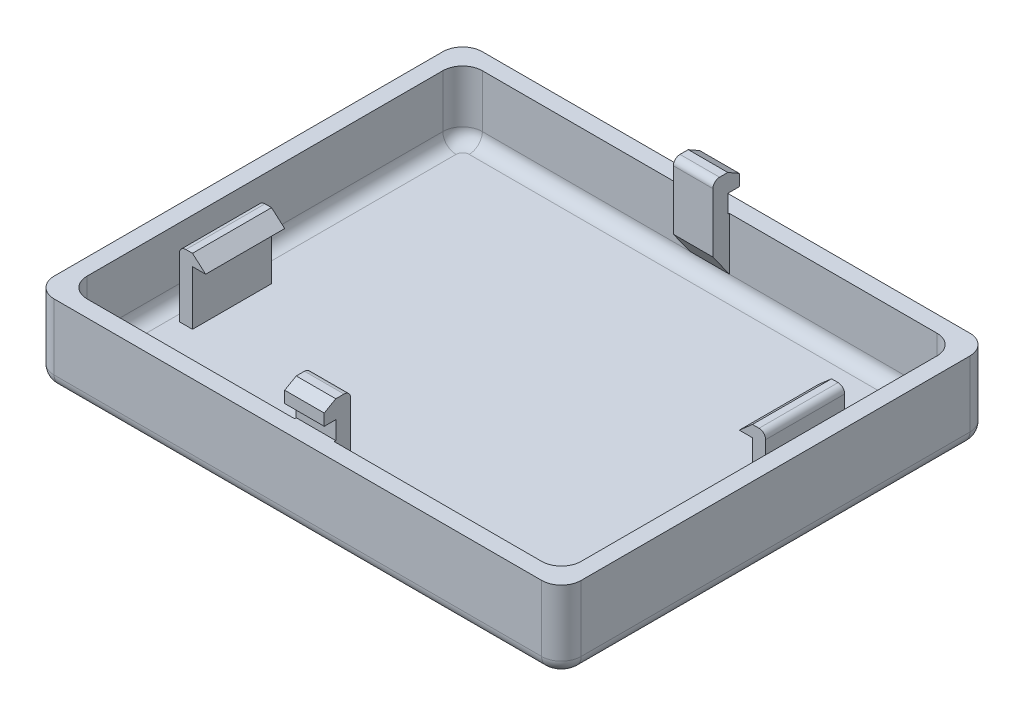
SolidWorks part; units mm, degrees
ref_plane "Front Plane" through (0, 0, 0) normal (0, 0, 1) x (1, 0, 0)
ref_plane "Top Plane" through (0, 0, 0) normal (0, 1, 0) x (1, 0, 0)
ref_plane "Right Plane" through (0, 0, 0) normal (1, 0, 0) x (0, 0, -1)
sketch "Sketch1" plane through (0, 0, 0) normal (0, 1, 0) x (1, 0, 0)
  line L0 (0, 0) -> (80, 0)
  line L1 (80, 0) -> (80, 65)
  line L2 (80, 65) -> (0, 65)
  line L3 (0, 65) -> (0, 0)
  dimension "D1" = 80
  dimension "D2" = 65
extrude "Boss-Extrude1" add sketch "Sketch1" along normal blind 12
sketch "Sketch2" plane through (0, 12, 0) normal (0, 1, 0) x (1, 0, 0)
  line L0 (0, 0) -> (77.5, 0)
  line L1 (0, 0) -> (80, 0) construction
  line L2 (77.5, 0) -> (77.5, 62.5)
  line L3 (77.5, 62.5) -> (2.5, 62.5)
  line L4 (2.5, 62.5) -> (2.5, 0)
  line L5 (2.5, 2.5) -> (77.5, 2.5)
  line L6 (0, 65) -> (0, 0) construction
  dimension "D1" = 60
  dimension "D2" = 75
  dimension "D3" = 2.5
  dimension "D4" = 2.5
extrude "Cut-Extrude1" cut sketch "Sketch2" along direction (0, 1, 0) on the side against the normal blind 10 contours L4 L5 L2 L3 region at (40, 12, -32.5)
fillet "Fillet4" radius 2 4 edges at (0, 0, -32.5) (40, 0, 0) (80, 0, -32.5) (40, 0, -65)
fillet "Fillet5" radius 3 12 edges at (79.4142, 0.5858, -0.5858) (79.4142, 0.5858, -64.4142) (0.5858, 0.5858, -64.4142) (0.5858, 0.5858, -0.5858) (80, 7, 0) (80, 7, -65) (0, 7, -65) (0, 7, 0) (2.5, 7, -2.5) (77.5, 7, -2.5) (77.5, 7, -62.5) (2.5, 7, -62.5)
sketch "Sketch3" plane through (0, 12, 0) normal (0, 1, 0) x (1, 0, 0)
  line L0 (0, 0) -> (80, 0)
  line L1 (80, 0) -> (80, 55)
  line L2 (80, 55) -> (0, 55)
  line L3 (0, 55) -> (0, 0)
  line L4 (1.5, 53.5) -> (1.5, 1.5)
  line L5 (1.5, 1.5) -> (78.5, 1.5)
  line L6 (78.5, 1.5) -> (78.5, 53.5)
  line L7 (78.5, 53.5) -> (1.5, 53.5)
  dimension "D1" = 55
  dimension "D2" = 1.5
extrude "Cut-Extrude2" [suppressed] cut sketch "Sketch3" against normal blind 1.5
fillet "Fillet7" [suppressed] radius 4
fillet "Fillet8" radius 2 8 edges at (76.6213, 2, -3.3787) (77.5, 2, -32.5) (76.6213, 2, -61.6213) (40, 2, -62.5) (3.3787, 2, -61.6213) (40, 2, -2.5) (3.3787, 2, -3.3787) (2.5, 2, -32.5)
sketch "Sketch5" plane through (0, 0, -62.5) normal (0, 0, 1) x (1, 0, 0)
  line L0 (37, 4) -> (43, 4)
  line L1 (5.5, 4) -> (74.5, 4) construction
  line L2 (43, 4) -> (43, 17.5)
  line L3 (43, 17.5) -> (37, 17.5)
  line L4 (37, 17.5) -> (37, 4)
  line L5 (0, 12) -> (0, 2) construction
  dimension "D1" = 6
  dimension "D2" = 37
  dimension "D3" = 13.5
extrude "Boss-Extrude2" add sketch "Sketch5" along normal blind 2.5
sketch "Sketch6" plane through (43, 0, 0) normal (1, 0, 0) x (0, 0, -1)
  line L0 (59.5, 12) -> (5.5, 12) construction
  line L1 (62.5, 17.5) -> (62.25, 17.5)
  line L2 (62.5, 17.5) -> (62.5, 12)
  line L3 (62.5, 12) -> (62.25, 12)
  line L4 (62.25, 17.5) -> (62.25, 12)
  dimension "D1" = 0.25
extrude "Cut-Extrude3" cut sketch "Sketch6" against normal up to next
sketch "Sketch7" plane through (43, 0, 0) normal (1, 0, 0) x (0, 0, -1)
  line L0 (62.25, 14.75) -> (64, 14.75)
  line L1 (62.25, 17.5) -> (62.25, 12) construction
  line L2 (64, 14.75) -> (64, 16.5)
  line L3 (64, 16.5) -> (62.25, 17.5)
  line L4 (62.25, 12) -> (62.5, 12) construction
  line L10 (62.5, 4) -> (62.5, 12)
  line L11 (62.5, 12) -> (62.25, 12)
  line L12 (62.25, 12) -> (62.25, 17.5)
  line L13 (62.25, 17.5) -> (60, 17.5)
  line L14 (60, 17.5) -> (60, 4)
  line L15 (60, 4) -> (62.5, 4)
  line L18 (62.25, 14.75) -> (62.25, 17.5)
  dimension "D1" = 1.75
  dimension "D2" = 1.75
  dimension "D4" = 2.75
  dimension "D3" = 0
extrude "Boss-Extrude3" add sketch "Sketch7" against normal blind 6
sketch "Sketch8" plane through (43, 0, 0) normal (1, 0, 0) x (0, 0, -1)
  line L0 (62.5, 4) -> (60, 7.5)
  line L1 (60, 4) -> (60, 17.5) construction
  line L2 (60, 7.5) -> (60, 4)
  line L3 (60, 4) -> (62.5, 4)
  line L6 (62.5, 12) -> (60, 12)
  line L7 (60, 12) -> (60, 7.5)
  line M11 (60, 17.5) -> (60, 4)
  line M12 (60, 4) -> (62.5, 4)
  dimension "D1" = 4.5
extrude "Cut-Extrude4" cut sketch "Sketch8" against normal up to next contours L0 M12 M11 region at (43, 5.1667, -60.8333)
sketch "Sketch10" plane through (0, 0, -2.5) normal (0, 0, -1) x (-1, 0, 0)
  line L0 (-43, 4) -> (-43, 17.5)
  line L1 (-74.5, 4) -> (-5.5, 4) construction
  line L2 (-43, 17.5) -> (-37, 17.5)
  line L3 (-37, 17.5) -> (-37, 4)
  line L4 (-37, 4) -> (-43, 4)
  line L5 (-80, 12) -> (-80, 2) construction
  dimension "D1" = 37
  dimension "D2" = 6
  dimension "D3" = 13.5
extrude "Boss-Extrude4" add sketch "Sketch10" along normal blind 2.5
sketch "Sketch11" plane through (37, 0, 0) normal (-1, 0, 0) x (0, 0, 1)
  line L1 (-2.5, 17.5) -> (-2.75, 17.5)
  line L2 (-2.5, 17.5) -> (-2.5, 12)
  line L3 (-2.5, 12) -> (-2.75, 12)
  line L4 (-2.75, 17.5) -> (-2.75, 12)
  dimension "D1" = 0.25
extrude "Cut-Extrude5" cut sketch "Sketch11" against normal up to next
sketch "Sketch12" plane through (37, 0, 0) normal (-1, 0, 0) x (0, 0, 1)
  line L0 (-2.75, 14.75) -> (-1, 14.75)
  line L1 (-2.75, 17.5) -> (-2.75, 12) construction
  line L2 (-1, 14.75) -> (-1, 16.5)
  line L3 (-1, 16.5) -> (-2.75, 17.5)
  line L4 (-2.75, 12) -> (-2.5, 12) construction
  line L11 (-2.5, 4) -> (-2.5, 12)
  line L12 (-2.5, 12) -> (-2.75, 12)
  line L13 (-2.75, 12) -> (-2.75, 17.5)
  line L14 (-2.75, 17.5) -> (-5, 17.5)
  line L15 (-5, 17.5) -> (-5, 4)
  line L16 (-5, 4) -> (-2.5, 4)
  line L19 (-2.75, 14.75) -> (-2.75, 17.5)
  dimension "D1" = 1.75
  dimension "D2" = 1.75
  dimension "D3" = 2.75
  dimension "D4" = 0
extrude "Boss-Extrude5" add sketch "Sketch12" against normal blind 6
sketch "Sketch13" plane through (37, 0, 0) normal (-1, 0, 0) x (0, 0, 1)
  line L0 (-2.5, 4) -> (-5, 7.5)
  line L1 (-5, 4) -> (-5, 17.5) construction
  line L3 (-5, 7.5) -> (-5, 4)
  line L4 (-5, 4) -> (-2.5, 4)
  line L5 (-2.75, 12) -> (-5, 12)
  line L6 (-5, 12) -> (-5, 7.5)
  line M11 (-5, 17.5) -> (-5, 4)
  line M12 (-5, 4) -> (-2.5, 4)
  dimension "D1" = 4.5
extrude "Cut-Extrude6" cut sketch "Sketch13" against normal blind 6 contours L0 M12 M11 region at (37, 5.1667, -4.1667)
sketch "Sketch14" plane through (0, 2, 0) normal (0, 1, 0) x (1, 0, 0)
  line L0 (4.5, 59.5) -> (4.5, 5.5) construction
  line L1 (5.5, 16.5) -> (7.5, 16.5)
  line L2 (5.5, 16.5) -> (5.5, 28.5)
  line L3 (5.5, 28.5) -> (7.5, 28.5)
  line L4 (7.5, 16.5) -> (7.5, 28.5)
  line L5 (5.5, 4.5) -> (74.5, 4.5) construction
  dimension "D1" = 1
  dimension "D2" = 2
  dimension "D3" = 12
  dimension "D4" = 12
extrude "Boss-Extrude7" add sketch "Sketch14" along normal blind 10
sketch "Sketch15" plane through (7.5, 0, 0) normal (1, 0, 0) x (0, 0, -1)
  line L0 (28.5, 12) -> (28.5, 2) construction
  line L1 (16.5, 12) -> (28.5, 12)
  line L2 (16.5, 12) -> (16.5, 10.25)
  line L3 (16.5, 10.25) -> (28.5, 10.25)
  line L4 (28.5, 12) -> (28.5, 10.25)
  dimension "D1" = 1.75
extrude "Boss-Extrude8" add sketch "Sketch15" along normal blind 2
sketch "Sketch16" plane through (0, 2, 0) normal (0, 1, 0) x (1, 0, 0)
  line L0 (75.5, 5.5) -> (75.5, 59.5) construction
  line L1 (74.5, 36.5) -> (72.5, 36.5)
  line L2 (74.5, 36.5) -> (74.5, 48.5)
  line L3 (74.5, 48.5) -> (72.5, 48.5)
  line L4 (72.5, 36.5) -> (72.5, 48.5)
  line L5 (74.5, 60.5) -> (5.5, 60.5) construction
  dimension "D1" = 1
  dimension "D2" = 2
  dimension "D3" = 12
  dimension "D4" = 12
extrude "Boss-Extrude9" add sketch "Sketch16" along normal blind 10
sketch "Sketch17" plane through (72.5, 0, 0) normal (-1, 0, 0) x (0, 0, 1)
  line L0 (-36.5, 12) -> (-36.5, 2) construction
  line L1 (-48.5, 12) -> (-36.5, 12)
  line L2 (-48.5, 12) -> (-48.5, 10.25)
  line L3 (-48.5, 10.25) -> (-36.5, 10.25)
  line L4 (-36.5, 12) -> (-36.5, 10.25)
  dimension "D1" = 1.75
extrude "Boss-Extrude10" add sketch "Sketch17" along normal blind 2
fillet "Fillet9" radius 1 4 edges at (40, 17.5, -60) (40, 17.5, -5) (74.5, 12, -42.5) (5.5, 12, -22.5)
sketch "Sketch18" plane through (0, 0, -16.5) normal (0, 0, 1) x (1, 0, 0)
  line L2 (6.5, 12) -> (9.5, 12) construction
  line L3 (7.5, 12) -> (9.5, 10.25)
  line L4 (9.5, 10.25) -> (7.5, 10.25) construction
  line L6 (7.5, 12) -> (9.5, 12)
  line L7 (9.5, 12) -> (9.5, 10.25)
extrude "Cut-Extrude7" cut sketch "Sketch18" against normal up to next
sketch "Sketch19" plane through (0, 0, -36.5) normal (0, 0, 1) x (1, 0, 0)
  line L0 (72.5, 10.25) -> (72.5, 12)
  line L1 (70.5, 12) -> (73.5, 12) construction
  line L2 (72.5, 12) -> (70.5, 10.25)
  line L3 (70.5, 10.25) -> (72.5, 10.25) construction
  line L4 (70.5, 10.25) -> (70.5, 12) construction
  line L5 (70.5, 10.25) -> (70.5, 12)
  line L6 (70.5, 12) -> (72.5, 12)
  line M3 (73.5, 12) -> (70.5, 12)
  line M4 (70.5, 12) -> (70.5, 10.25)
extrude "Cut-Extrude8" cut sketch "Sketch19" against normal up to next contours L2 M3 M4 region at (71.1667, 11.4167, -36.5)
